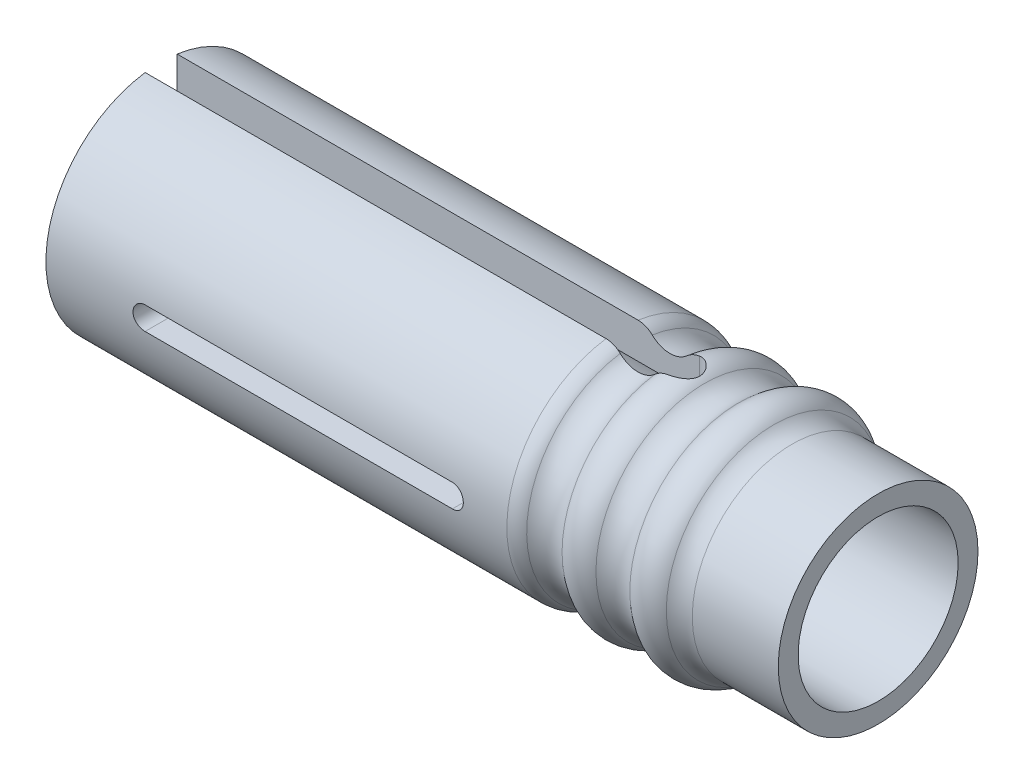
SolidWorks part; units mm, degrees
ref_plane "Front Plane" through (0, 0, 0) normal (0, 0, 1) x (1, 0, 0)
ref_plane "Top Plane" through (0, 0, 0) normal (0, 1, 0) x (1, 0, 0)
ref_plane "Right Plane" through (0, 0, 0) normal (1, 0, 0) x (0, 0, -1)
sketch "Sketch1" plane through (0, 0, 0) normal (0, 0, 1) x (1, 0, 0)
  line L0 (0, 0) -> (71.12, 0)
  line L1 (0, 11.43) -> (45.72, 11.43)
  line L2 (62.5904, 9.906) -> (71.12, 9.906)
  line L3 (71.12, 9.906) -> (71.12, 0)
  line L4 (0, 11.43) -> (0, 0)
  arc A0 (45.72, 11.43) -> (47.1255, 10.8656) centre (45.72, 9.398) cw
  arc A1 (47.1255, 10.8656) -> (50.5623, 10.795) centre (48.8823, 12.7) ccw
  arc A2 (50.5623, 10.795) -> (53.9224, 10.795) centre (52.2424, 8.89) cw
  arc A3 (53.9224, 10.795) -> (57.2825, 10.795) centre (55.6025, 12.7) ccw
  arc A4 (57.2825, 10.795) -> (60.7765, 10.668) centre (58.9626, 8.89) cw
  arc A5 (60.7765, 10.668) -> (62.5904, 9.906) centre (62.5904, 12.446) ccw
  dimension "D4" = 2.032
  dimension "D7" = 2.54
  dimension "D1" = 71.12
  dimension "D2" = 11.43
  dimension "D3" = 45.72
  dimension "D5" = 9.906
  dimension "D6" = 10.16
revolve "Revolve1" add sketch "Sketch1" angle 360 about L0
sketch "Sketch7" plane through (0, 0, 0) normal (0, 0, 1) x (1, 0, 0)
  line L0 (9.779, 0) -> (40.259, 0) construction
  line L1 (9.779, 1.143) -> (40.259, 1.143)
  line L2 (9.779, -1.143) -> (40.259, -1.143)
  line L3 (0, 11.43) -> (0, -11.43) construction
  arc A0 (9.779, 1.143) -> (9.779, -1.143) centre (9.779, 0) ccw
  arc A1 (40.259, -1.143) -> (40.259, 1.143) centre (40.259, 0) ccw
  point P2 (25.019, 0)
  dimension "D1" = 2.286
  dimension "D2" = 8.636
  dimension "D3" = 30.48
extrude "Cut-Extrude1" cut sketch "Sketch7" along normal through all
sketch "Sketch8" plane through (0, 0, 0) normal (0, 1, 0) x (1, 0, 0)
  line L0 (0, 11.43) -> (0, -11.43) construction
  line L1 (0, -1.5875) -> (51.8269, -1.5875)
  line L2 (0, -1.5875) -> (0, 1.5875)
  line L3 (0, 1.5875) -> (51.8269, 1.5875)
  line L5 (53.9224, -10.795) -> (53.9224, 10.795) construction
  arc A2 (51.8269, 1.5875) -> (51.8269, -1.5875) centre (51.8269, 0) cw
  point P6 (0, 0)
  dimension "D1" = 0.508
  dimension "D2" = 3.175
extrude "Cut-Extrude2" cut sketch "Sketch8" along normal through all
hole_wizard "5/8 (0.625) Diameter Hole1" positions "Sketch4" profile "Sketch6" hole size "5/8" standard "ANSI Inch" end condition through all
sketch "Sketch4" plane through (71.12, 0, 0) normal (1, 0, 0) x (0, 0, -1)
  point P0 (0, 0)
sketch "Sketch6" plane through (71.12, 0, 0) normal (0, 1, 0) x (0, 0, -1)
  line L0 (0, 0) -> (0, 71.12)
  line L1 (0, 71.12) -> (7.9375, 71.12)
  line L2 (7.9375, 71.12) -> (7.9375, 0)
  line L5 (7.9375, 0) -> (0, 0)
  line L11 (0, -6.35) -> (0, 107.95) construction
  dimension "Thru Hole Dia." = 15.875
  dimension "Thru Hole Depth" = 71.12
